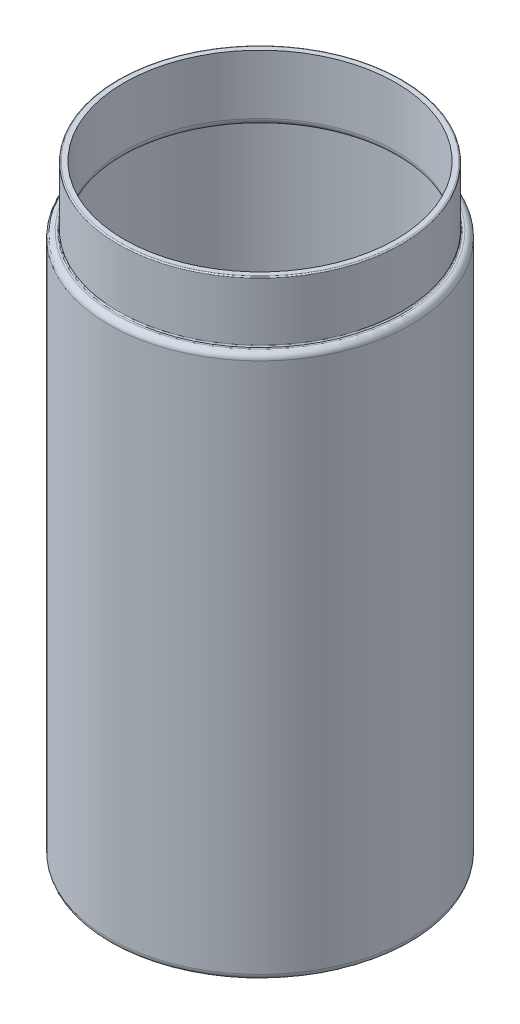
SolidWorks part; units mm, degrees
ref_plane "Front Plane" through (0, 0, 0) normal (0, 0, 1) x (1, 0, 0)
ref_plane "Top Plane" through (0, 0, 0) normal (0, 1, 0) x (1, 0, 0)
ref_plane "Right Plane" through (0, 0, 0) normal (1, 0, 0) x (0, 0, -1)
sketch "Sketch1" plane through (0, 0, 0) normal (0, 1, 0) x (1, 0, 0)
  circle A0 centre (0, 0) radius 25
  dimension "D1" = 50
extrude "Boss-Extrude1" add sketch "Sketch1" along normal blind 90
sketch "Sketch2" plane through (0, 90, 0) normal (0, 1, 0) x (1, 0, 0)
  circle A0 centre (0, 0) radius 23.5
  dimension "D1" = 47
extrude "Boss-Extrude2" add sketch "Sketch2" along normal blind 10
fillet "Fillet1" radius 1 2 edges at (0, 90, 25) (0, 0, 25)
fillet "Fillet2" radius 0.2 2 edges at (0, 90, 23.5) (0, 100, 23.5)
shell "Shell1" thickness 1 removed face at (0, 100, 23.3)
